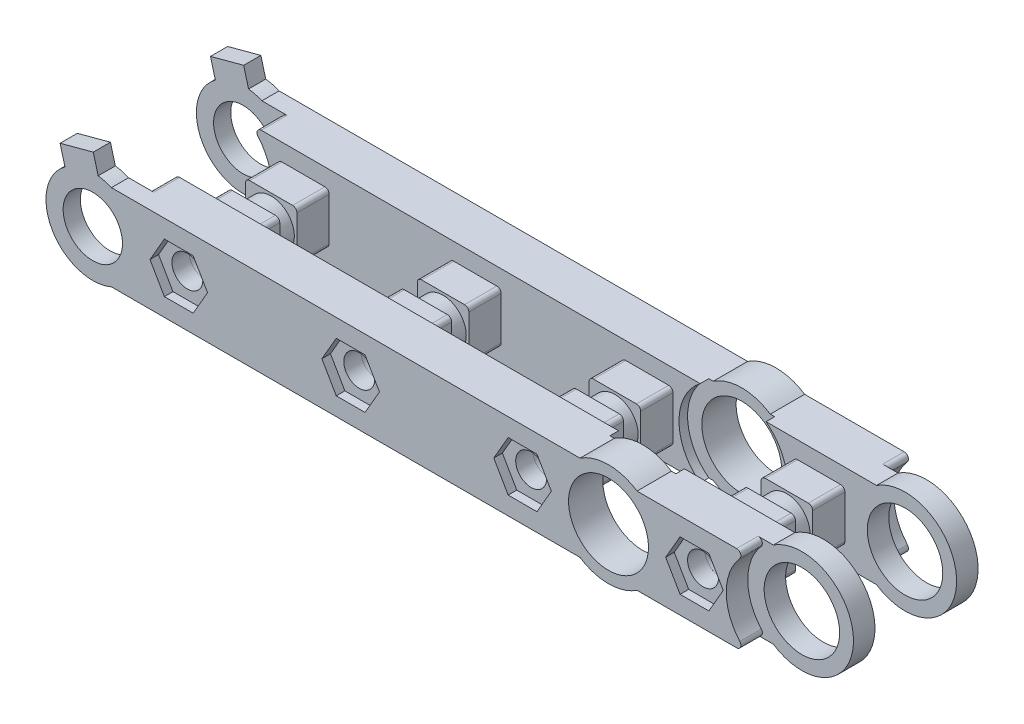
SolidWorks part; units mm, degrees
material "ABS"
ref_plane "正面" through (0, 0, 0) normal (0, 0, 1) x (1, 0, 0)
ref_plane "平面" through (0, 0, 0) normal (0, 1, 0) x (1, 0, 0)
ref_plane "右側面" through (0, 0, 0) normal (1, 0, 0) x (0, 0, -1)
sketch "ｽｹｯﾁ1" plane through (0, 0, 0) normal (0, 0, 1) x (1, 0, 0)
  line L0 (0, 0) -> (-20, 0) construction
  line L1 (3.64, -3.64) -> (-3.64, -3.64) construction
  line L2 (3.64, -3.64) -> (3.64, 3.64) construction
  line L3 (3.64, 3.64) -> (-3.64, 3.64) construction
  line L4 (-3.64, -3.64) -> (-3.64, 3.64) construction
  line L5 (3.64, -3.64) -> (-3.64, 3.64) construction
  line L6 (3.64, 3.64) -> (-3.64, -3.64) construction
  line L7 (-20, 0) -> (-40, 0) construction
  line L8 (-40, 0) -> (-60, 0) construction
  line L9 (-60, 0) -> (-80, 0) construction
  line L10 (-80, 0) -> (-100, 0) construction
  line L11 (0, 5) -> (-20, 5) construction
  line L18 (-20, 5) -> (-40, 5) construction
  line L19 (-40, 5) -> (-60, 5) construction
  line L20 (-60, 5) -> (-77.8315, 5) construction
  line L21 (-80, 5) -> (-100, 5) construction
  line L22 (0, -5) -> (-20, -5) construction
  line L23 (-20, -5) -> (-40, -5) construction
  line L24 (-40, -5) -> (-60, -5) construction
  line L25 (-60, -5) -> (-77.8315, -5) construction
  line L26 (-80, -5) -> (-100, -5) construction
  line L27 (-102.1685, 5) -> (-80, 5) construction
  line L28 (-77.8315, 5) -> (-60, 5)
  line L29 (-60, 5) -> (-40, 5)
  line L30 (-40, 5) -> (-20, 5)
  line L31 (-20, 5) -> (-3.3166, 5)
  line L32 (-3.3166, -5) -> (-20, -5)
  line L33 (-20, -5) -> (-40, -5)
  line L34 (-40, -5) -> (-60, -5)
  line L35 (-60, -5) -> (-77.8315, -5)
  line L36 (-80, -5) -> (-102.1685, -5) construction
  line L39 (-60, 5) -> (-80, 5) construction
  line L40 (-60, -5) -> (-80, -5) construction
  line L41 (-80, 5) -> (-77.8315, 5) construction
  line L42 (-80, -5) -> (-77.8315, -5) construction
  circle A0 centre (-10, 0) radius 1.8
  circle A1 centre (-30, 0) radius 1.8
  circle A2 centre (-50, 0) radius 1.8
  circle A3 centre (-70, 0) radius 1.8
  circle A4 centre (-90, 0) radius 1.8 construction
  circle A5 centre (-100, 0) radius 3.45 construction
  arc A6 (-3.3166, -5) -> (-3.3166, 5) centre (0, 0) ccw
  arc A7 (-102.1685, 5) -> (-102.1685, -5) centre (-100, 0) ccw construction
  circle A8 centre (0, 0) radius 4.39
  circle A9 centre (-80, 0) radius 3.45
  arc A11 (-77.8315, 5) -> (-77.8315, -5) centre (-80, 0) ccw
  point P0 (0, 0)
  dimension "D8" = 3.6
  dimension "D9" = 6.9
  dimension "D10" = 12
  dimension "D13" = 10.9
  dimension "D3" = 8.78
  dimension "D4" = 6.9
  dimension "D5" = 10.9
  dimension "D1" = 7.28
  dimension "D2" = 7.28
  dimension "D7" = 20
  dimension "D11" = 5
  dimension "D12" = 5
extrude "ﾎﾞｽ - 押し出し1" add sketch "ｽｹｯﾁ1" along normal blind 2
sketch "ｽｹｯﾁ2" plane through (0, 0, 0) normal (0, 0, -1) x (-1, 0, 0)
  line L19 (77.8315, 5) -> (60, 5)
  line L20 (60, 5) -> (40, 5)
  line L21 (40, 5) -> (20, 5)
  line L22 (20, 5) -> (3.3166, 5)
  line L23 (3.3166, -5) -> (20, -5)
  line L24 (20, -5) -> (40, -5)
  line L25 (40, -5) -> (60, -5)
  line L26 (60, -5) -> (77.8315, -5)
  line L29 (74.902, 5) -> (60, 5)
  line L30 (60, 5) -> (40, 5)
  line L31 (40, 5) -> (20, 5)
  line L32 (20, 5) -> (3.3166, 5)
  line L33 (3.3166, -5) -> (20, -5)
  line L34 (20, -5) -> (40, -5)
  line L35 (40, -5) -> (60, -5)
  line L36 (60, -5) -> (74.902, -5)
  circle A1 centre (30, 0) radius 1.8
  circle A2 centre (30, 0) radius 1.8
  circle A3 centre (10, 0) radius 1.8
  circle A4 centre (10, 0) radius 1.8
  arc A7 (75.2768, 4.1691) -> (75.2768, -4.1691) centre (80, 0) ccw
  circle A9 centre (70, 0) radius 1.8
  circle A10 centre (70, 0) radius 1.8
  circle A11 centre (50, 0) radius 1.8
  circle A12 centre (50, 0) radius 1.8
  arc A14 (3.3166, 5) -> (3.3166, -5) centre (0, 0) ccw
  arc A16 (3.3166, 5) -> (3.3166, -5) centre (0, 0) ccw
  circle A18 centre (0, 0) radius 4.39 construction
  circle A19 centre (0, 0) radius 4.39
  arc A20 (75.2768, -4.1691) -> (74.902, -5) centre (74.902, -4.5) cw
  arc A21 (75.2768, 4.1691) -> (74.902, 5) centre (74.902, 4.5) ccw
  arc A22 (77.8315, -5) -> (77.8315, 5) centre (80, 0) ccw
  dimension "D4" = 0.5
  dimension "D3" = 6.3
  dimension "D1" = 0
  dimension "D2" = 0
  dimension "D6" = 0
  dimension "D7" = 0
  dimension "D8" = 0
extrude "ﾎﾞｽ - 押し出し2" add sketch "ｽｹｯﾁ2" along normal blind 3
ref_plane "平面1" through (0, 0, -17.5) normal (0, 0, 1) x (1, 0, 0)
ref_plane "平面2" through (0, 0, -7.75) normal (0, 0, 1) x (1, 0, 0)
sketch "ｽｹｯﾁ3" plane through (0, 0, 2) normal (0, 0, 1) x (1, 0, 0)
  line L0 (-80, 0) -> (-80, 5.45) construction
  line L2 (-80, 0) -> (-81.4106, 5.2643) construction
  line L3 (-79.9446, 7.5206) -> (-79.0128, 4.0433)
  line L4 (-79.9446, 7.5206) -> (-83.8083, 6.4853)
  line L5 (-79.0128, 4.0433) -> (-82.8765, 3.008)
  line L6 (-83.8083, 6.4853) -> (-82.8765, 3.008)
  line L7 (-79.9446, 7.5206) -> (-82.8765, 3.008) construction
  line L8 (-79.0128, 4.0433) -> (-83.8083, 6.4853) construction
  arc A1 (-77.8315, 5) -> (-77.8315, -5) centre (-80, 0) ccw construction
  dimension "D1" = 1.8
  dimension "D2" = 4
  dimension "D3" = 15
extrude "ﾎﾞｽ - 押し出し3" add sketch "ｽｹｯﾁ3" against normal up to surface (2 mm away) up to face at (-76.55, 0, 0)
sketch "ｽｹｯﾁ4" plane through (0, 0, -17.5) normal (0, 0, 1) x (1, 0, 0)
  line L19 (-60, 5) -> (-77.8315, 5)
  line L20 (-40, 5) -> (-60, 5)
  line L21 (-20, 5) -> (-40, 5)
  line L22 (-3.3166, 5) -> (-20, 5)
  line L23 (-20, -5) -> (-3.3166, -5)
  line L24 (-40, -5) -> (-20, -5)
  line L25 (-60, -5) -> (-40, -5)
  line L26 (-77.8315, -5) -> (-60, -5)
  line L29 (-60, 5) -> (-77.8315, 5)
  line L30 (-40, 5) -> (-60, 5)
  line L31 (-20, 5) -> (-40, 5)
  line L32 (-3.3166, 5) -> (-20, 5)
  line L33 (-20, -5) -> (-3.3166, -5)
  line L34 (-40, -5) -> (-20, -5)
  line L35 (-60, -5) -> (-40, -5)
  line L36 (-77.8315, -5) -> (-60, -5)
  circle A0 centre (0, 0) radius 4.39 construction
  circle A1 centre (-30, 0) radius 1.8
  circle A2 centre (-30, 0) radius 1.8
  circle A3 centre (-10, 0) radius 1.8
  circle A4 centre (-10, 0) radius 1.8
  circle A5 centre (-80, 0) radius 3.45 construction
  circle A7 centre (-80, 0) radius 3.45
  circle A9 centre (-70, 0) radius 1.8
  circle A10 centre (-70, 0) radius 1.8
  circle A11 centre (-50, 0) radius 1.8
  circle A12 centre (-50, 0) radius 1.8
  circle A13 centre (0, 0) radius 4.39
  arc A14 (-3.3166, -5) -> (-3.3166, 5) centre (0, 0) ccw
  arc A15 (-77.8315, 5) -> (-77.8315, -5) centre (-80, 0) ccw
  arc A16 (-3.3166, -5) -> (-3.3166, 5) centre (0, 0) ccw
  arc A21 (-77.8315, 5) -> (-77.8315, -5) centre (-80, 0) ccw
  dimension "D1" = 0
  dimension "D2" = 0
  dimension "D6" = 0
  dimension "D7" = 0
  dimension "D8" = 0
extrude "ﾎﾞｽ - 押し出し4" add sketch "ｽｹｯﾁ4" along normal blind 2 separate body
sketch "ｽｹｯﾁ5" plane through (0, 0, -15.5) normal (0, 0, 1) x (1, 0, 0)
  line L18 (-74.902, -5) -> (-60, -5)
  line L19 (-60, -5) -> (-40, -5)
  line L20 (-40, -5) -> (-20, -5)
  line L21 (-20, -5) -> (-3.3166, -5)
  line L22 (-3.3166, 5) -> (-20, 5)
  line L23 (-20, 5) -> (-40, 5)
  line L24 (-40, 5) -> (-60, 5)
  line L25 (-60, 5) -> (-74.902, 5)
  line L28 (-74.902, -5) -> (-60, -5)
  line L29 (-60, -5) -> (-40, -5)
  line L30 (-40, -5) -> (-20, -5)
  line L31 (-20, -5) -> (-3.3166, -5)
  line L32 (-3.3166, 5) -> (-20, 5)
  line L33 (-20, 5) -> (-40, 5)
  line L34 (-40, 5) -> (-60, 5)
  line L35 (-60, 5) -> (-74.902, 5)
  circle A0 centre (0, 0) radius 4.39 construction
  circle A1 centre (-10, 0) radius 1.8
  circle A2 centre (-10, 0) radius 1.8
  circle A3 centre (-30, 0) radius 1.8
  circle A4 centre (-30, 0) radius 1.8
  circle A5 centre (-50, 0) radius 1.8
  circle A6 centre (-50, 0) radius 1.8
  circle A7 centre (-70, 0) radius 1.8
  circle A8 centre (-70, 0) radius 1.8
  circle A11 centre (0, 0) radius 4.39
  arc A12 (-3.3166, -5) -> (-3.3166, 5) centre (0, 0) ccw
  arc A14 (-3.3166, -5) -> (-3.3166, 5) centre (0, 0) ccw
  arc A20 (-75.2768, -4.1691) -> (-74.902, -5) centre (-74.902, -4.5) ccw
  arc A22 (-75.2768, -4.1691) -> (-74.902, -5) centre (-74.902, -4.5) ccw
  arc A23 (-75.2768, -4.1691) -> (-75.2768, 4.1691) centre (-80, 0) ccw
  arc A24 (-75.2768, -4.1691) -> (-75.2768, 4.1691) centre (-80, 0) ccw
  arc A25 (-74.902, 5) -> (-75.2768, 4.1691) centre (-74.902, 4.5) ccw
  arc A26 (-74.902, 5) -> (-75.2768, 4.1691) centre (-74.902, 4.5) ccw
  dimension "D1" = 0
  dimension "D2" = 0
  dimension "D4" = 0
  dimension "D5" = 0
  dimension "D7" = 0
extrude "ﾎﾞｽ - 押し出し5" add sketch "ｽｹｯﾁ5" along normal blind 3
sketch "ｽｹｯﾁ12" plane through (0, 0, 2) normal (0, 0, 1) x (1, 0, 0)
  circle A0 centre (0, 0) radius 6.3
  dimension "D1" = 12.6
extrude "ｶｯﾄ - 押し出し5" cut sketch "ｽｹｯﾁ12" against normal blind 2.5
sketch "ｽｹｯﾁ14" plane through (0, 0, -3) normal (0, 0, -1) x (-1, 0, 0)
  circle A1 centre (0, 0) radius 6.3
  circle A2 centre (0, 0) radius 6.3
  dimension "D1" = 0
extrude "ｶｯﾄ - 押し出し7" cut sketch "ｽｹｯﾁ14" against normal blind 1
fillet "ﾌｨﾚｯﾄ1" radius 0.5 4 edges at (-3.8328, -5, 0.75) (-3.8328, -5, -2.5) (-3.8328, 5, -2.5) (-3.8328, 5, 0.75)
sketch "ｽｹｯﾁ15" plane through (0, 0, -17.5) normal (0, 0, -1) x (-1, 0, 0)
  circle A1 centre (0, 0) radius 6.3
  circle A2 centre (0, 0) radius 6.3
  dimension "D1" = 0
extrude "ｶｯﾄ - 押し出し8" cut sketch "ｽｹｯﾁ15" against normal blind 2.5
sketch "ｽｹｯﾁ16" plane through (0, 0, -12.5) normal (0, 0, 1) x (1, 0, 0)
  circle A1 centre (0, 0) radius 6.3
  circle A2 centre (0, 0) radius 6.3
  dimension "D1" = 0
extrude "ｶｯﾄ - 押し出し9" cut sketch "ｽｹｯﾁ16" against normal blind 1
fillet "ﾌｨﾚｯﾄ2" radius 0.5 4 edges at (-3.8328, -5, -16.25) (-3.8328, -5, -13) (-3.8328, 5, -16.25) (-3.8328, 5, -13)
sketch "ｽｹｯﾁ6" plane through (0, 0, -17.5) normal (0, 0, -1) x (-1, 0, 0)
  line L4 (79.9446, 7.5206) -> (79.0128, 4.0433)
  line L5 (79.0128, 4.0433) -> (82.8765, 3.008)
  line L6 (82.8765, 3.008) -> (83.8083, 6.4853)
  line L7 (83.8083, 6.4853) -> (79.9446, 7.5206)
  line L8 (79.9446, 7.5206) -> (79.0128, 4.0433)
  line L9 (79.0128, 4.0433) -> (82.8765, 3.008)
  line L10 (82.8765, 3.008) -> (83.8083, 6.4853)
  line L11 (83.8083, 6.4853) -> (79.9446, 7.5206)
  dimension "D1" = 0
extrude "ﾎﾞｽ - 押し出し6" add sketch "ｽｹｯﾁ6" against normal up to surface (2 mm away) up to face at (-77.0998, 0, -15.5)
sketch "ｽｹｯﾁ7" plane through (0, 0, -3) normal (0, 0, -1) x (-1, 0, 0)
  line L0 (26.9, -3.1) -> (26.9, 3.1)
  line L1 (6.9, -3.1) -> (13.1, -3.1)
  line L2 (6.9, -3.1) -> (6.9, 3.1)
  line L3 (6.9, 3.1) -> (13.1, 3.1)
  line L4 (13.1, -3.1) -> (13.1, 3.1)
  line L5 (6.9, -3.1) -> (13.1, 3.1) construction
  line L6 (6.9, 3.1) -> (13.1, -3.1) construction
  line L7 (26.9, -3.1) -> (33.1, -3.1)
  line L8 (26.9, 3.1) -> (33.1, 3.1)
  line L9 (33.1, -3.1) -> (33.1, 3.1)
  line L10 (26.9, -3.1) -> (33.1, 3.1) construction
  line L11 (26.9, 3.1) -> (33.1, -3.1) construction
  line L12 (46.9, -3.1) -> (46.9, 3.1)
  line L13 (46.9, -3.1) -> (53.1, -3.1)
  line L14 (46.9, 3.1) -> (53.1, 3.1)
  line L15 (53.1, -3.1) -> (53.1, 3.1)
  line L16 (46.9, -3.1) -> (53.1, 3.1) construction
  line L17 (46.9, 3.1) -> (53.1, -3.1) construction
  line L18 (66.9, -3.1) -> (66.9, 3.1)
  line L19 (66.9, -3.1) -> (73.1, -3.1)
  line L20 (66.9, 3.1) -> (73.1, 3.1)
  line L21 (73.1, -3.1) -> (73.1, 3.1)
  line L22 (66.9, -3.1) -> (73.1, 3.1) construction
  line L23 (66.9, 3.1) -> (73.1, -3.1) construction
  line L30 (5.098, 5) -> (77.8315, 5) construction
  line L31 (5.098, 5) -> (77.8315, 5) construction
  line L32 (5.098, 5) -> (77.8315, 5) construction
  circle A0 centre (30, 0) radius 1.8 construction
  circle A1 centre (50, 0) radius 1.8 construction
  circle A2 centre (70, 0) radius 1.8 construction
  point P0 (10, 0)
  point P7 (30, 0)
  point P8 (50, 0)
  point P9 (70, 0)
  dimension "D1" = 6.2
  dimension "D2" = 6.2
extrude "ｶｯﾄ - 押し出し1" cut sketch "ｽｹｯﾁ7" against normal blind 2
sketch "ｽｹｯﾁ8" plane through (0, 0, -12.5) normal (0, 0, 1) x (1, 0, 0)
  line L0 (-13, -3) -> (-7, -3)
  line L1 (-7, -3) -> (-7, 3)
  line L2 (-7, 3) -> (-13, 3)
  line L3 (-13, 3) -> (-13, -3)
  line L4 (-13.1, -3.1) -> (-6.9, -3.1)
  line L5 (-13.1, 3.1) -> (-13.1, -3.1)
  line L6 (-6.9, 3.1) -> (-13.1, 3.1)
  line L7 (-6.9, -3.1) -> (-6.9, 3.1)
  line L8 (-13.1, -3.1) -> (-6.9, -3.1) construction
  line L9 (-13.1, 3.1) -> (-13.1, -3.1) construction
  line L10 (-6.9, 3.1) -> (-13.1, 3.1) construction
  line L11 (-6.9, -3.1) -> (-6.9, 3.1) construction
  line L12 (-26.9, -3.1) -> (-26.9, 3.1)
  line L13 (-26.9, 3.1) -> (-33.1, 3.1)
  line L14 (-33.1, 3.1) -> (-33.1, -3.1)
  line L15 (-33.1, -3.1) -> (-26.9, -3.1)
  line L16 (-26.9, -3.1) -> (-26.9, 3.1) construction
  line L17 (-26.9, 3.1) -> (-33.1, 3.1) construction
  line L18 (-33.1, 3.1) -> (-33.1, -3.1) construction
  line L19 (-33.1, -3.1) -> (-26.9, -3.1) construction
  line L28 (-66.9, -3.1) -> (-66.9, 3.1)
  line L29 (-66.9, 3.1) -> (-73.1, 3.1)
  line L30 (-73.1, 3.1) -> (-73.1, -3.1)
  line L31 (-73.1, -3.1) -> (-66.9, -3.1)
  line L32 (-66.9, -3.1) -> (-66.9, 3.1) construction
  line L33 (-66.9, 3.1) -> (-73.1, 3.1) construction
  line L34 (-73.1, 3.1) -> (-73.1, -3.1) construction
  line L35 (-73.1, -3.1) -> (-66.9, -3.1) construction
  line L36 (-46.9, -3.1) -> (-46.9, 3.1)
  line L37 (-53.1, -3.1) -> (-46.9, -3.1)
  line L38 (-53.1, 3.1) -> (-53.1, -3.1)
  line L39 (-46.9, 3.1) -> (-53.1, 3.1)
  line L40 (-46.9, -3.1) -> (-46.9, 3.1) construction
  line L41 (-53.1, -3.1) -> (-46.9, -3.1) construction
  line L42 (-53.1, 3.1) -> (-53.1, -3.1) construction
  line L43 (-46.9, 3.1) -> (-53.1, 3.1) construction
  line L44 (-27, -3) -> (-27, 3)
  line L45 (-27, 3) -> (-33, 3)
  line L46 (-33, 3) -> (-33, -3)
  line L47 (-33, -3) -> (-27, -3)
  line L52 (-67, -3) -> (-67, 3)
  line L53 (-67, 3) -> (-73, 3)
  line L54 (-73, 3) -> (-73, -3)
  line L55 (-73, -3) -> (-67, -3)
  line L56 (-47, -3) -> (-47, 3)
  line L57 (-47, 3) -> (-53, 3)
  line L58 (-53, 3) -> (-53, -3)
  line L59 (-53, -3) -> (-47, -3)
  circle A1 centre (-70, 0) radius 1.8 construction
  circle A2 centre (-50, 0) radius 1.8 construction
  circle A3 centre (-30, 0) radius 1.8 construction
  circle A4 centre (-10, 0) radius 1.8 construction
  circle A6 centre (-70, 0) radius 1.8
  circle A7 centre (-50, 0) radius 1.8
  circle A8 centre (-30, 0) radius 1.8
  circle A9 centre (-10, 0) radius 1.8
  dimension "D1" = 0
  dimension "D2" = 0
  dimension "D4" = 0
  dimension "D5" = 0
  dimension "D6" = 0.1
extrude "ﾎﾞｽ - 押し出し7" add sketch "ｽｹｯﾁ8" along normal up to surface (11.5 mm away) up to face at (-8.2, 0, -1)
sketch "ｽｹｯﾁ9" plane through (0, 0, -7.75) normal (0, 0, 1) x (1, 0, 0)
  line L12 (-27, -3) -> (-27, 3)
  line L13 (-27, 3) -> (-33, 3)
  line L14 (-33, 3) -> (-33, -3)
  line L15 (-33, -3) -> (-27, -3)
  line L16 (-27, -3) -> (-27, 3)
  line L17 (-27, 3) -> (-33, 3)
  line L18 (-33, 3) -> (-33, -3)
  line L19 (-33, -3) -> (-27, -3)
  line L20 (-13, -3) -> (-7, -3)
  line L21 (-7, -3) -> (-7, 3)
  line L22 (-7, 3) -> (-13, 3)
  line L23 (-13, 3) -> (-13, -3)
  line L24 (-13, -3) -> (-7, -3)
  line L25 (-7, -3) -> (-7, 3)
  line L26 (-7, 3) -> (-13, 3)
  line L27 (-13, 3) -> (-13, -3)
  line L28 (-47, -3) -> (-47, 3)
  line L29 (-47, 3) -> (-53, 3)
  line L30 (-53, 3) -> (-53, -3)
  line L31 (-53, -3) -> (-47, -3)
  line L32 (-47, -3) -> (-47, 3)
  line L33 (-47, 3) -> (-53, 3)
  line L34 (-53, 3) -> (-53, -3)
  line L35 (-53, -3) -> (-47, -3)
  line L36 (-67, -3) -> (-67, 3)
  line L37 (-67, 3) -> (-73, 3)
  line L38 (-73, 3) -> (-73, -3)
  line L39 (-73, -3) -> (-67, -3)
  line L40 (-67, -3) -> (-67, 3)
  line L41 (-67, 3) -> (-73, 3)
  line L42 (-73, 3) -> (-73, -3)
  line L43 (-73, -3) -> (-67, -3)
  circle A1 centre (-70, 0) radius 2.7
  circle A3 centre (-50, 0) radius 2.7
  circle A5 centre (-30, 0) radius 2.7
  circle A7 centre (-10, 0) radius 2.7
  dimension "D6" = 5.4
  dimension "D2" = 0
  dimension "D3" = 0
  dimension "D4" = 0
  dimension "D5" = 0
extrude "ｶｯﾄ - 押し出し2" cut sketch "ｽｹｯﾁ9" against normal blind 1 and the other way blind 1
sketch "ｽｹｯﾁ10" plane through (0, 0, 2) normal (0, 0, 1) x (1, 0, 0)
  line L1 (-11.6743, 2.9) -> (-13.3486, 0)
  line L2 (-13.3486, 0) -> (-11.6743, -2.9)
  line L3 (-11.6743, -2.9) -> (-8.3257, -2.9)
  line L4 (-8.3257, -2.9) -> (-6.6514, 0)
  line L5 (-6.6514, 0) -> (-8.3257, 2.9)
  line L6 (-8.3257, 2.9) -> (-11.6743, 2.9)
  line L33 (-31.6743, -2.9) -> (-28.3257, -2.9)
  line L34 (-28.3257, -2.9) -> (-26.6514, 0)
  line L35 (-26.6514, 0) -> (-28.3257, 2.9)
  line L36 (-28.3257, 2.9) -> (-31.6743, 2.9)
  line L37 (-31.6743, 2.9) -> (-33.3486, 0)
  line L38 (-33.3486, 0) -> (-31.6743, -2.9)
  line L39 (-51.6743, -2.9) -> (-48.3257, -2.9)
  line L40 (-48.3257, -2.9) -> (-46.6514, 0)
  line L41 (-46.6514, 0) -> (-48.3257, 2.9)
  line L42 (-48.3257, 2.9) -> (-51.6743, 2.9)
  line L43 (-51.6743, 2.9) -> (-53.3486, 0)
  line L44 (-53.3486, 0) -> (-51.6743, -2.9)
  line L45 (-68.3257, -2.9) -> (-66.6514, 0)
  line L46 (-66.6514, 0) -> (-68.3257, 2.9)
  line L47 (-68.3257, 2.9) -> (-71.6743, 2.9)
  line L48 (-71.6743, 2.9) -> (-73.3486, 0)
  line L49 (-73.3486, 0) -> (-71.6743, -2.9)
  line L50 (-71.6743, -2.9) -> (-68.3257, -2.9)
  circle A0 centre (-10, 0) radius 2.9 construction
  circle A1 centre (-30, 0) radius 2.9 construction
  circle A2 centre (-50, 0) radius 2.9 construction
  circle A3 centre (-70, 0) radius 2.9 construction
  dimension "D1" = 5.8
extrude "ｶｯﾄ - 押し出し3" cut sketch "ｽｹｯﾁ10" against normal blind 1
sketch "ｽｹｯﾁ11" plane through (0, 0, -17.5) normal (0, 0, -1) x (-1, 0, 0)
  circle A0 centre (10, 0) radius 3.25
  circle A1 centre (30, 0) radius 3.25
  circle A2 centre (50, 0) radius 3.25
  circle A3 centre (70, 0) radius 3.25
  dimension "D1" = 6.5
extrude "ｶｯﾄ - 押し出し4" cut sketch "ｽｹｯﾁ11" against normal blind 1.5
sketch "ｽｹｯﾁ17" plane through (0, 0, 2) normal (0, 0, 1) x (1, 0, 0)
  line L0 (-30, 0) -> (-10, 0) construction
  circle A0 centre (-20, 0) radius 4.65
  dimension "D1" = 9.3
extrude "ｶｯﾄ - 押し出し10" cut sketch "ｽｹｯﾁ17" against normal through all
sketch "ｽｹｯﾁ18" plane through (0, 0, -3) normal (0, 0, -1) x (-1, 0, 0)
  circle A0 centre (20, 0) radius 6.3
  dimension "D1" = 12.6
extrude "ｶｯﾄ - 押し出し11" cut sketch "ｽｹｯﾁ18" against normal blind 1
sketch "ｽｹｯﾁ19" plane through (0, 0, -12.5) normal (0, 0, 1) x (1, 0, 0)
  circle A1 centre (-20, 0) radius 6.3
  circle A2 centre (-20, 0) radius 6.3
  dimension "D1" = 0
extrude "ｶｯﾄ - 押し出し12" cut sketch "ｽｹｯﾁ19" against normal blind 1
sketch "ｽｹｯﾁ20" plane through (0, 0, -13.5) normal (0, 0, 1) x (1, 0, 0)
  line L0 (-23.3166, 5) -> (-16.6834, 5)
  line L1 (-5.098, 5) -> (-77.8315, 5) construction
  line L2 (-23.3166, -5) -> (-16.6834, -5)
  line L3 (-77.8315, -5) -> (-5.098, -5) construction
  arc A0 (-23.3166, -5) -> (-16.6834, -5) centre (-20, 0) ccw
  arc A1 (-16.6834, 5) -> (-23.3166, 5) centre (-20, 0) ccw
  dimension "D1" = 12
extrude "ﾎﾞｽ - 押し出し8" add sketch "ｽｹｯﾁ20" against normal up to surface (4 mm away) up to face at (-15.35, 0, -17.5)
sketch "ｽｹｯﾁ21" plane through (0, 0, -2) normal (0, 0, -1) x (-1, 0, 0)
  line L1 (23.3166, -5) -> (16.6834, -5)
  line L2 (23.3166, -5) -> (16.6834, -5)
  line L3 (16.6834, 5) -> (23.3166, 5)
  line L4 (16.6834, 5) -> (23.3166, 5)
  arc A1 (16.6834, -5) -> (23.3166, -5) centre (20, 0) ccw
  arc A2 (16.6834, -5) -> (23.3166, -5) centre (20, 0) ccw
  arc A3 (23.3166, 5) -> (16.6834, 5) centre (20, 0) ccw
  arc A4 (23.3166, 5) -> (16.6834, 5) centre (20, 0) ccw
  dimension "D1" = 0
  dimension "D2" = 0
extrude "ﾎﾞｽ - 押し出し9" add sketch "ｽｹｯﾁ21" against normal up to surface (4 mm away) up to face at (-15.35, 0, 2)
sketch "ｽｹｯﾁ22" plane through (0, 0, -2) normal (0, 0, -1) x (-1, 0, 0)
  line L2 (5.098, 5) -> (3.3166, 5)
  line L3 (3.3166, -5) -> (5.098, -5)
  line L4 (5.098, 5) -> (3.3166, 5)
  line L5 (3.3166, -5) -> (5.098, -5)
  circle A0 centre (0, 0) radius 4.39 construction
  circle A1 centre (0, 0) radius 4.39
  arc A4 (3.3166, 5) -> (3.3166, -5) centre (0, 0) ccw
  arc A5 (4.7232, -4.1691) -> (5.098, -5) centre (5.098, -4.5) ccw
  arc A6 (4.7232, -4.1691) -> (4.7232, 4.1691) centre (0, 0) ccw
  arc A7 (5.098, 5) -> (4.7232, 4.1691) centre (5.098, 4.5) ccw
  arc A8 (3.3166, 5) -> (3.3166, -5) centre (0, 0) ccw
  arc A9 (4.7232, -4.1691) -> (5.098, -5) centre (5.098, -4.5) ccw
  arc A10 (4.7232, -4.1691) -> (4.7232, 4.1691) centre (0, 0) ccw
  arc A11 (5.098, 5) -> (4.7232, 4.1691) centre (5.098, 4.5) ccw
  dimension "D1" = 0
extrude "ﾎﾞｽ - 押し出し10" add sketch "ｽｹｯﾁ22" along normal up to surface (1 mm away) up to face at (-10, 0, -3)
sketch "ｽｹｯﾁ23" plane through (0, 0, -13.5) normal (0, 0, 1) x (1, 0, 0)
  line L2 (-3.3166, 5) -> (-5.098, 5)
  line L3 (-5.098, -5) -> (-3.3166, -5)
  line L4 (-3.3166, 5) -> (-5.098, 5)
  line L5 (-5.098, -5) -> (-3.3166, -5)
  circle A1 centre (0, 0) radius 4.39
  circle A2 centre (0, 0) radius 4.39
  arc A6 (-3.3166, -5) -> (-3.3166, 5) centre (0, 0) ccw
  arc A7 (-5.098, -5) -> (-4.7232, -4.1691) centre (-5.098, -4.5) ccw
  arc A8 (-4.7232, 4.1691) -> (-4.7232, -4.1691) centre (0, 0) ccw
  arc A9 (-4.7232, 4.1691) -> (-5.098, 5) centre (-5.098, 4.5) ccw
  arc A10 (-3.3166, -5) -> (-3.3166, 5) centre (0, 0) ccw
  arc A11 (-5.098, -5) -> (-4.7232, -4.1691) centre (-5.098, -4.5) ccw
  arc A12 (-4.7232, 4.1691) -> (-4.7232, -4.1691) centre (0, 0) ccw
  arc A13 (-4.7232, 4.1691) -> (-5.098, 5) centre (-5.098, 4.5) ccw
  dimension "D1" = 0
  dimension "D2" = 0
extrude "ﾎﾞｽ - 押し出し11" add sketch "ｽｹｯﾁ23" along normal up to surface (1 mm away) up to face at (-8.425, 0, -12.5)
fillet "ﾌｨﾚｯﾄ3" radius 0.5 32 edges at (-13, -3, -3.875) (-13, -3, -10.625) (-7, -3, -10.625) (-7, -3, -3.875) (-7, 3, -3.875) (-7, 3, -10.625) (-13, 3, -10.625) (-13, 3, -3.875) (-27, -3, -3.875) (-27, -3, -10.625) (-27, 3, -3.875) (-27, 3, -10.625) (-33, -3, -3.875) (-33, -3, -10.625) (-33, 3, -10.625) (-33, 3, -3.875) (-53, -3, -3.875) (-53, -3, -10.625) (-47, -3, -3.875) (-47, -3, -10.625) (-47, 3, -3.875) (-47, 3, -10.625) (-53, 3, -10.625) (-53, 3, -3.875) (-67, -3, -3.875) (-67, -3, -10.625) (-67, 3, -10.625) (-67, 3, -3.875) (-73, -3, -3.875) (-73, -3, -10.625) (-73, 3, -10.625) (-73, 3, -3.875)
